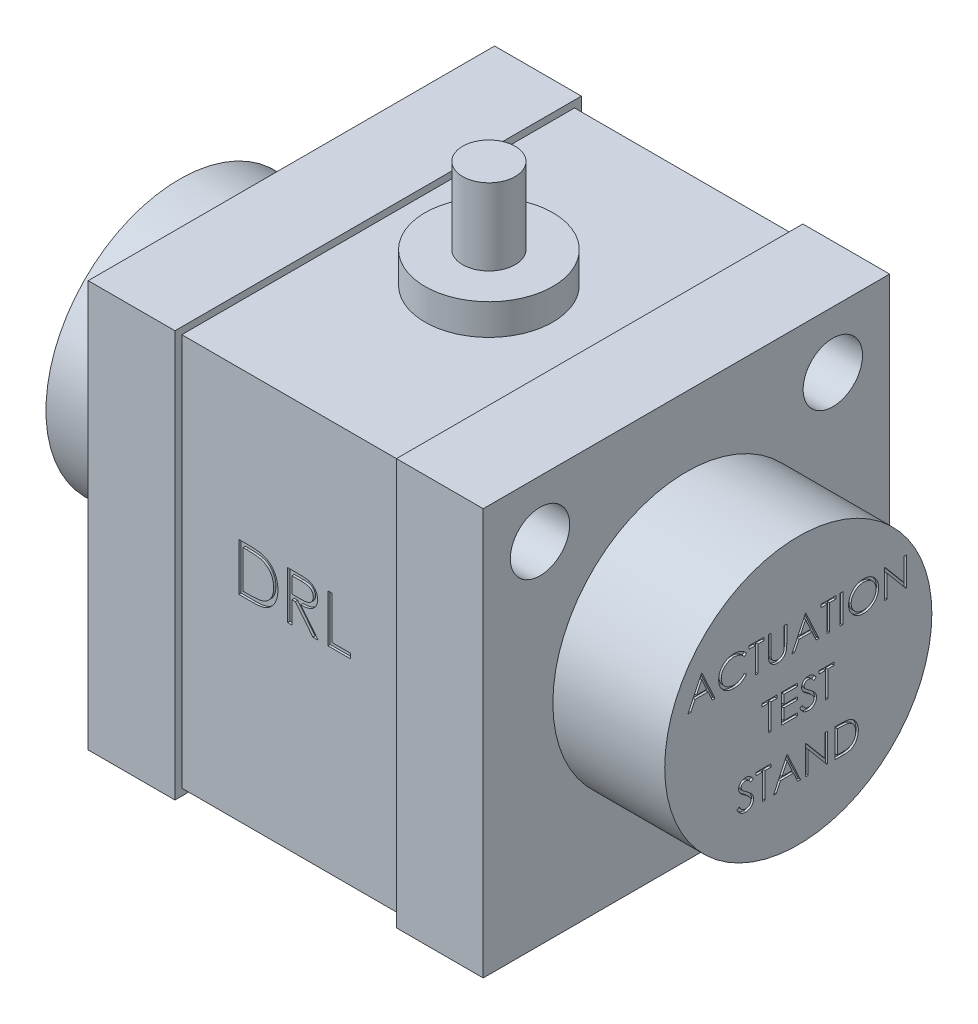
SolidWorks part; units mm, degrees
ref_plane "Front Plane" through (0, 0, 0) normal (0, 0, 1) x (1, 0, 0)
ref_plane "Top Plane" through (0, 0, 0) normal (0, 1, 0) x (1, 0, 0)
ref_plane "Right Plane" through (0, 0, 0) normal (1, 0, 0) x (0, 0, -1)
sketch "Sketch4" plane through (0, 0, 0) normal (1, 0, 0) x (0, 0, -1)
  line L0 (-21.844, 21.844) -> (21.844, 21.844)
  line L1 (-22.606, -22.606) -> (22.606, -22.606)
  line L2 (-22.606, -22.606) -> (-22.606, 22.606)
  line L3 (-22.606, 22.606) -> (22.606, 22.606)
  line L4 (22.606, -22.606) -> (22.606, 22.606)
  line L5 (-22.606, -22.606) -> (22.606, 22.606) construction
  line L6 (-22.606, 22.606) -> (22.606, -22.606) construction
  line L7 (21.844, -21.844) -> (21.844, 21.844)
  line L8 (-21.844, -21.844) -> (21.844, -21.844)
  line L9 (-21.844, -21.844) -> (-21.844, 21.844)
  point P0 (0, 0)
  dimension "D1" = 45.212
  dimension "D2" = 45.212
  dimension "D3" = 0.762
extrude "Boss-Extrude1" add sketch "Sketch4" against normal blind 9.652 contours L9 L8 L7 L0 | L1 L4 L3 L2 L8 L9 L0 L7 | L0 L7 L8 L9 | L2 L1 L4 L3 region at (0, 0, 0) region at (0, 0, 21.9666)
extrude "Boss-Extrude2" add sketch "Sketch4<3>" along normal blind 24.638 contours L9 L8 L7 L0 region at (0, 0, 0)
sketch "Sketch4<3>" plane through (0, 0, 0) normal (1, 0, 0) x (0, 0, -1) same geometry as "Sketch4"
extrude "Boss-Extrude3" add sketch "Sketch4<4>" along normal blind 9.652 from surface contours L9 L8 L7 L0 | L1 L4 L3 L2 L8 L9 L0 L7 region at (0, 0, 0) region at (0, 0, 21.9666) starting at face at (24.638, 0, 0)
sketch "Sketch4<4>" plane through (0, 0, 0) normal (1, 0, 0) x (0, 0, -1) same geometry as "Sketch4"
sketch "Sketch5" plane through (0, 21.844, 0) normal (0, 1, 0) x (1, 0, 0)
  line L0 (12.319, 21.844) -> (12.319, -21.844) construction
  line L1 (24.638, 21.844) -> (0, 21.844) construction
  line L2 (24.638, -21.844) -> (0, -21.844) construction
  circle A0 centre (12.319, 0) radius 7.112
  circle A1 centre (12.319, 0) radius 2.921
  dimension "D1" = 14.224
  dimension "D2" = 5.842
extrude "Boss-Extrude4" add sketch "Sketch5" along normal blind 3.4379 contours A0 L0 A1 | L0 A0 A1 | A1 L0 | L0 A1 | A1 | A0 region at (15.6984, 21.844, 0) region at (8.9396, 21.844, 0) region at (13.5587, 21.844, 0) region at (11.0793, 21.844, 0)
extrude "Boss-Extrude5" add sketch "Sketch5<3>" along normal blind 8.4963 from surface contours L0 A1 | A1 L0 region at (13.5587, 21.844, 0) region at (11.0793, 21.844, 0) starting at face at (12.319, 25.2819, 7.112)
sketch "Sketch5<3>" plane through (0, 21.844, 0) normal (0, 1, 0) x (1, 0, 0) same geometry as "Sketch5"
sketch "Sketch6" plane through (34.29, 0, 0) normal (1, 0, 0) x (0, 0, -1)
  line L0 (-22.606, 22.606) -> (-22.606, -22.606) construction
  line L1 (22.606, 22.606) -> (-22.606, 22.606) construction
  line L2 (0, 22.606) -> (0, -22.606) construction
  line L3 (22.606, -22.606) -> (-22.606, -22.606) construction
  circle A0 centre (-16.2865, 16.2865) radius 3.302
  circle A1 centre (16.2865, 16.2865) radius 3.302
  dimension "D3" = 6.604
  dimension "D1" = 6.3195
  dimension "D2" = 6.3195
extrude "Cut-Extrude1" cut sketch "Sketch6" against normal through all
sketch "Sketch7" plane through (34.29, 0, 0) normal (1, 0, 0) x (0, 0, -1)
  circle A0 centre (0, 0) radius 14.859
  dimension "D1" = 29.718
extrude "Boss-Extrude6" add sketch "Sketch7" along normal blind 12.446
extrude "Boss-Extrude7" add sketch "Sketch7<2>" against normal blind 12.446 from surface starting at face at (-9.652, 16.2865, 12.9845)
sketch "Sketch7<2>" plane through (34.29, 0, 0) normal (1, 0, 0) x (0, 0, -1) same geometry as "Sketch7"
sketch "Sketch8" plane through (46.736, 0, 0) normal (1, 0, 0) x (0, 0, -1)
  line L0 (-14.3429, 3.8823) -> (14.3429, 3.8823) construction
  line L1 (0, 14.859) -> (0, -14.859) construction
  circle A0 centre (0, 0) radius 14.859 construction
  circle A1 centre (0, 0) radius 14.859 construction
  text T0 "ACTUATION\r\nTEST\r\nSTAND"
extrude "Cut-Extrude2" cut sketch "Sketch8" against normal blind 0.254
sketch "Sketch9" plane through (-22.098, 0, 0) normal (-1, 0, 0) x (0, 0, 1)
  line L0 (0, 14.859) -> (0, -14.859) construction
  line L1 (-13.8383, 5.4122) -> (13.8383, 5.4122) construction
  circle A1 centre (0, 0) radius 14.859
  circle A2 centre (0, 0) radius 14.859 construction
  text T0 "August \r\nStinks\r\n"
  dimension "D1" = 0
extrude "Cut-Extrude3" cut sketch "Sketch9" against normal blind 0.254
sketch "Sketch10" plane through (0, 0, 21.844) normal (0, 0, 1) x (1, 0, 0)
  line L0 (0, 0) -> (24.638, 0) construction
  line L1 (24.638, 22.606) -> (24.638, -22.606) construction
  text T0 "DRL" font "Century Gothic" height in points 20
extrude "Cut-Extrude4" cut sketch "Sketch10" against normal blind 0.254
sketch "Sketch11" plane through (0, 0, -21.844) normal (0, 0, -1) x (-1, 0, 0)
  line L0 (0, 0) -> (-24.638, 0) construction
  line L1 (-24.638, -21.844) -> (-24.638, 21.844) construction
  text T0 "DRL" font "Century Gothic" height in points 20
extrude "Cut-Extrude5" cut sketch "Sketch11" against normal blind 0.254
